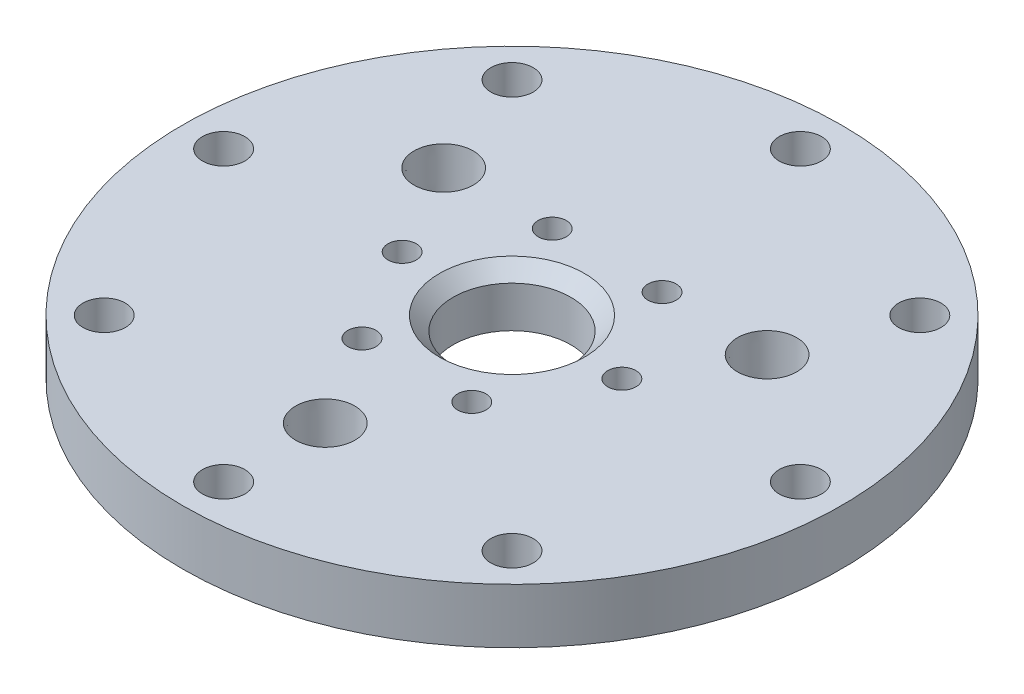
SolidWorks part; units mm, degrees
material "AISI Type 316L stainless steel"
ref_plane "Front Plane" through (0, 0, 0) normal (0, 0, 1) x (1, 0, 0)
ref_plane "Top Plane" through (0, 0, 0) normal (0, 1, 0) x (1, 0, 0)
ref_plane "Right Plane" through (0, 0, 0) normal (1, 0, 0) x (0, 0, -1)
sketch "Sketch1" plane through (0, 0, 0) normal (0, 1, 0) x (1, 0, 0)
  circle A0 centre (0, 0) radius 76.2
  dimension "D1" = 152.4
extrude "Boss-Extrude1" add sketch "Sketch1" along normal blind 12.7
hole_wizard "3/8 Clearance Hole1" positions "Sketch2" profile "Sketch3" hole size "3/8" standard "ANSI Inch" end condition through all
sketch "Sketch2" plane through (0, 12.7, 0) normal (0, 1, 0) x (1, 0, 0)
  line L1 (66.675, 0) -> (47.1463, 47.1463)
  line L2 (47.1463, 47.1463) -> (0, 66.675)
  line L3 (0, 66.675) -> (-47.1463, 47.1463)
  line L4 (-47.1463, 47.1463) -> (-66.675, 0)
  line L5 (-66.675, 0) -> (-47.1463, -47.1463)
  line L6 (-47.1463, -47.1463) -> (0, -66.675)
  line L7 (0, -66.675) -> (47.1463, -47.1463)
  line L8 (47.1463, -47.1463) -> (66.675, 0)
  line L9 (0, 0) -> (66.675, 0) construction
  circle A0 centre (0, 0) radius 66.675 construction
  point P3 (66.675, 0)
  point P4 (47.1463, 47.1463)
  point P5 (0, 66.675)
  point P6 (-47.1463, 47.1463)
  point P7 (-66.675, 0)
  point P8 (-47.1463, -47.1463)
  point P9 (0, -66.675)
  point P10 (47.1463, -47.1463)
  dimension "D1" = 133.35
sketch "Sketch3" plane through (47.1463, 12.7, 47.1463) normal (1, 0, 0) x (0, 0, 1)
  line L0 (0, 0) -> (0, 12.7)
  line L1 (0, 12.7) -> (4.9022, 12.7)
  line L2 (4.9022, 12.7) -> (4.9022, 0)
  line L5 (4.9022, 0) -> (0, 0)
  line L11 (0, -6.35) -> (0, 107.95) construction
  dimension "Thru Hole Dia." = 9.8044
  dimension "Thru Hole Depth" = 12.7
hole_wizard "1/4 Clearance Hole1" positions "Sketch4" profile "Sketch5" hole size "1/4" standard "ANSI Inch" end condition through all
sketch "Sketch4" plane through (0, 12.7, 0) normal (0, 1, 0) x (1, 0, 0)
  line L2 (25.4, 0) -> (12.7, 21.997)
  line L3 (12.7, 21.997) -> (-12.7, 21.997)
  line L4 (-12.7, 21.997) -> (-25.4, 0)
  line L5 (-25.4, 0) -> (-12.7, -21.997)
  line L6 (-12.7, -21.997) -> (12.7, -21.997)
  line L7 (12.7, -21.997) -> (25.4, 0)
  circle A0 centre (0, 0) radius 25.4 construction
  point P5 (25.4, 0)
  point P6 (12.7, 21.997)
  point P7 (-12.7, 21.997)
  point P8 (-25.4, 0)
  point P9 (-12.7, -21.997)
  point P10 (12.7, -21.997)
  dimension "D1" = 50.8
sketch "Sketch5" plane through (12.7, 12.7, 21.997) normal (1, 0, 0) x (0, 0, 1)
  line L0 (0, 0) -> (0, 12.7)
  line L1 (0, 12.7) -> (3.2639, 12.7)
  line L2 (3.2639, 12.7) -> (3.2639, 0)
  line L5 (3.2639, 0) -> (0, 0)
  line L11 (0, -6.35) -> (0, 107.95) construction
  dimension "Thru Hole Dia." = 6.5278
  dimension "Thru Hole Depth" = 12.7
hole_wizard "1/4 NPT Tapped Hole1" positions "Sketch6" profile "Sketch7" size "1/4" standard "ANSI Inch" end condition through all
sketch "Sketch6" plane through (0, 12.7, 0) normal (0, 1, 0) x (1, 0, 0)
  line L1 (0, -43.18) -> (37.395, 21.59)
  line L2 (37.395, 21.59) -> (-37.395, 21.59)
  line L3 (-37.395, 21.59) -> (0, -43.18)
  line L4 (0, 0) -> (0, -43.18) construction
  circle A0 centre (0, 0) radius 43.18 construction
  point P3 (0, -43.18)
  point P4 (37.395, 21.59)
  point P5 (-37.395, 21.59)
  dimension "D1" = 43.18
sketch "Sketch7" plane through (-37.395, 12.7, -21.59) normal (1, 0, 0) x (0, 0, 1)
  line L0 (0, 0) -> (0, 12.7)
  line L1 (0, 12.7) -> (5.5626, 12.7)
  line L2 (-6.558, 9.906) -> (-6.8546, 0) construction
  line L3 (5.5626, 12.7) -> (5.5626, 9.906)
  line L4 (5.5626, 9.906) -> (6.558, 9.906)
  line L5 (6.558, 9.906) -> (6.8546, 0)
  line L7 (6.8546, 0) -> (0, 0)
  line L8 (0, -6.35) -> (0, 107.95) construction
  line L11 (-5.5626, 9.906) -> (-6.558, 9.906) construction
  dimension "Thru Tap Drill Dia." = 11.1252
  dimension "Thru Tap Drill Depth" = 12.7
  dimension "Thread Dia." = 13.7092
  dimension "Thread Angle" = 3.43
  dimension "Thread Depth" = 9.906
sketch "Sketch8" plane through (0, 12.7, 0) normal (0, 1, 0) x (1, 0, 0)
  circle A0 centre (0, 0) radius 13.6
  dimension "D1" = 27.2
extrude "Cut-Extrude1" cut sketch "Sketch8" against normal through all
chamfer "Chamfer1" distance 3.175 angle 45 1 edges at (0, 12.7, 13.6)
